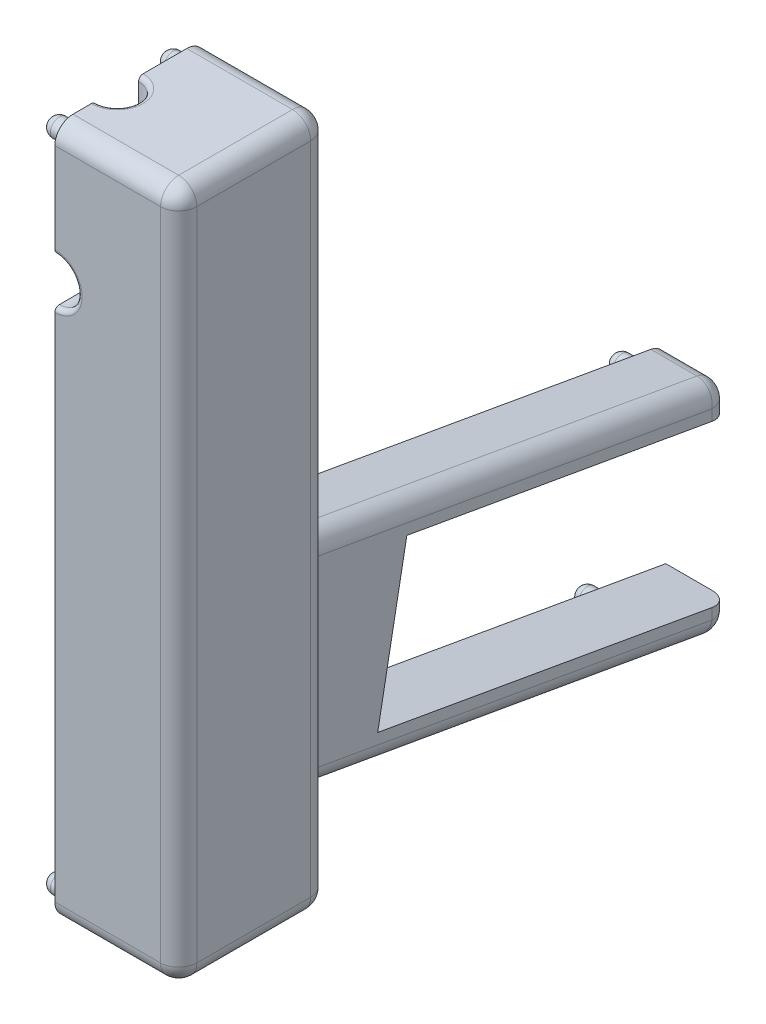
SolidWorks part; units mm, degrees
ref_plane "Front Plane" through (0, 0, 0) normal (0, 0, 1) x (1, 0, 0)
ref_plane "Top Plane" through (0, 0, 0) normal (0, 1, 0) x (1, 0, 0)
ref_plane "Right Plane" through (0, 0, 0) normal (1, 0, 0) x (0, 0, -1)
sketch "Sketch1" plane through (0, 0, 0) normal (0, 1, 0) x (1, 0, 0)
  line L1 (0, 0) -> (27.305, 0)
  line L2 (0, 0) -> (0, 33.1)
  line L3 (0, 33.1) -> (27.305, 33.1)
  line L4 (27.305, 0) -> (27.305, 33.1)
  dimension "D1" = 27.305
  dimension "D2" = 33.1
extrude "Boss-Extrude1" add sketch "Sketch1" along normal blind 152.4
sketch "Sketch2" plane through (0, 0, 0) normal (-1, 0, 0) x (0, 0, 1)
  line L0 (0, 152.4) -> (0, 0) construction
  line L1 (-6.35, 146.05) -> (-26.75, 146.05)
  line L2 (-6.35, 146.05) -> (-6.35, 6.35)
  line L3 (-6.35, 6.35) -> (-26.75, 6.35)
  line L4 (-26.75, 146.05) -> (-26.75, 6.35)
  line L5 (-33.1, 152.4) -> (0, 152.4) construction
  line L6 (-33.1, 152.4) -> (-33.1, 0) construction
  line L7 (-33.1, 0) -> (0, 0) construction
  dimension "D1" = 6.35
  dimension "D2" = 6.35
  dimension "D3" = 6.35
  dimension "D4" = 6.35
extrude "Cut-Extrude1" cut sketch "Sketch2" against normal blind 19.05
sketch "Sketch3" plane through (0, 0, 0) normal (0, 0, 1) x (1, 0, 0)
  line L0 (0, 152.4) -> (0, 0) construction
  line L1 (0, 127.555) -> (0, 117.555)
  arc A0 (0, 127.555) -> (0, 117.555) centre (0, 122.555) cw
  dimension "D1" = 29.845
extrude "HitLED" cut sketch "Sketch3" against normal up to next
sketch "Sketch6" plane through (19.05, 0, 0) normal (-1, 0, 0) x (0, 0, 1)
  line L0 (-15.7, 107.95) -> (-15.7, 33.02)
  line L1 (-9.35, 107.95) -> (-23.75, 107.95)
  line L2 (-9.35, 107.95) -> (-9.35, 33.02)
  line L3 (-9.35, 33.02) -> (-23.75, 33.02)
  line L4 (-23.75, 107.95) -> (-23.75, 33.02)
  line L5 (-17.4, 33.02) -> (-17.4, 107.95)
  line L7 (-6.35, 146.05) -> (-26.75, 146.05) construction
  line L8 (-26.75, 146.05) -> (-26.75, 6.35) construction
  line M8 (-6.35, 146.05) -> (-26.75, 146.05)
  dimension "D1" = 38.1
  dimension "D2" = 3
  dimension "D3" = 1.7
  dimension "D4" = 6.35
  dimension "D5" = 6.35
  dimension "D6" = 74.93
extrude "PCB" add sketch "Sketch6" along normal blind 6.35 contours L3 L2 L0 M8 | L3 L5 L1 L4 region at (19.05, 70.485, -12.525) region at (19.05, 70.485, -20.575)
sketch "Sketch16" plane through (0, 0, 0) normal (-1, 0, 0) x (0, 0, 1)
  line L1 (-33.1, 152.4) -> (0, 152.4) construction
  line L2 (0, 117.555) -> (0, 0) construction
  line L3 (-33.1, 0) -> (0, 0) construction
  line L5 (-33.1, 152.4) -> (-33.1, 0) construction
  circle A0 centre (-4, 148.4) radius 2
  circle A1 centre (-4, 4) radius 2
  circle A2 centre (-29.1, 148.4) radius 2
  circle A3 centre (-29.1, 4) radius 2
  dimension "D1" = 4
  dimension "D3" = 4
  dimension "D2" = 4
  dimension "D4" = 4
extrude "PressFit" add sketch "Sketch16" along normal blind 5
fillet "Fillet-PressFit" radius 2 4 edges at (-5, 4, -27.1) (-5, 4, -2) (-5, 148.4, -27.1) (-5, 148.4, -2)
sketch "Sketch23" plane through (0, 0, -25.4) normal (-1, 0, 0) x (0, 0, 1)
  line L4 (-7.7, 61.1358) -> (-7.7, 12.7)
  line L5 (-7.7, 12.7) -> (-109.3, -5.2148)
  line L6 (-109.3, -5.2148) -> (-109.3, 43.221)
  line L7 (-109.3, 43.221) -> (-7.7, 61.1358)
  dimension "D1" = 47.7
  dimension "D2" = 12.7
extrude "Butt" add sketch "Sketch23" against normal blind 14.175
sketch "Sketch20" plane through (0, 0, 0) normal (-1, 0, 0) x (0, 0, 1)
  line L0 (-63.4356, 49.3389) -> (-57.0033, 14.9332)
  line L1 (-63.4356, 49.3389) -> (-130.4061, 37.5302)
  line L2 (-57.0033, 14.9332) -> (-123.9738, 3.1245)
  line L6 (-130.4061, 37.5302) -> (-134.7, 36.7731)
  line L10 (-123.9738, 3.1245) -> (-134.7, 1.2331)
  line L11 (-134.7, 1.2331) -> (-134.7, 36.7731)
  dimension "D2" = 35
extrude "BatteryPack" cut sketch "Sketch20" against normal blind 14.175
sketch "Sketch22" plane through (0, 0, 0) normal (-1, 0, 0) x (0, 0, 1)
  line L0 (-63.4356, 49.3389) -> (-134.7, 36.7731) construction
  line L2 (-134.7, 1.2331) -> (-57.0033, 14.9332) construction
  line L4 (-57.0033, 14.9332) -> (-63.4356, 49.3389) construction
  circle A0 centre (-128.067, 41.1666) radius 2
  circle A1 centre (-120.4429, 0.5231) radius 2
  dimension "D1" = 3.175
  dimension "D2" = 3.175
  dimension "D3" = 65.0325
  dimension "D4" = 65.0073
extrude "PressFit - Bottom" add sketch "Sketch22" along normal blind 5
sketch "Sketch25" plane through (0, 146.05, 0) normal (0, -1, 0) x (1, 0, 0)
  line L0 (0, -6.35) -> (0, -26.75) construction
  line L1 (0, -9.05) -> (0, -18.45)
  line L2 (19.05, -26.75) -> (0, -26.75) construction
  arc A0 (0, -9.05) -> (0, -18.45) centre (0, -13.75) cw
  dimension "D1" = 13
extrude "IRLED" cut sketch "Sketch25" against normal up to next
fillet "Fillet - Body" radius 4 17 edges at (14.175, -1.9908, -134.7) (14.175, 39.997, -134.7) (7.0875, 43.221, -134.7) (7.0875, -5.2148, -134.7) (14.175, 52.1784, -83.9) (14.175, 3.7426, -83.9) (7.0875, 12.7, -33.1) (14.175, 36.9179, -33.1) (7.0875, 61.1358, -33.1) (13.6525, 152.4, -33.1) (13.6525, 152.4, 0) (27.305, 152.4, -16.55) (27.305, 76.2, -33.1) (27.305, 0, -16.55) (13.6525, 0, -33.1) (13.6525, 0, 0) (27.305, 76.2, 0)
fillet "Fillet-PressFit-Bottom" radius 2 2 edges at (-5, 0.5231, -118.4429) (-5, 41.1666, -126.067)
fillet "Fillet-LED's" radius 1 2 edges at (4.7, 152.4, -13.75) (5, 122.555, 0)
sketch "Sketch26" plane through (0, 0, 0) normal (-1, 0, 0) x (0, 0, 1)
  line L0 (-46.718, 58.7346) -> (-53.6116, 57.5191)
  line L1 (-53.6116, 57.5191) -> (-52.9865, 53.9738)
  line L2 (-52.9865, 53.9738) -> (-46.0928, 55.1893)
  line L3 (-46.0928, 55.1893) -> (-46.718, 58.7346)
  line L4 (-36.4054, 60.553) -> (-131.3946, 43.8039) construction
  point P6 (-46.4054, 56.962)
  dimension "D1" = 3.6
  dimension "D2" = 7
  dimension "D3" = 10
  dimension "D4" = 0
extrude "Cut-Extrude2" cut sketch "Sketch26" against normal blind 3.5
sketch "Sketch27" plane through (0, 0, 0) normal (-1, 0, 0) x (0, 0, 1)
  line L0 (-40.1594, 56.2356) -> (-58.92, 52.9276)
  line L1 (-58.92, 52.9276) -> (-58.6248, 51.2534)
  line L2 (-58.6248, 51.2534) -> (-39.8642, 54.5614)
  line L3 (-39.8642, 54.5614) -> (-40.1594, 56.2356)
  line L6 (-52.9865, 53.9738) -> (-46.0928, 55.1893) construction
  line L7 (-46.0928, 55.1893) -> (-46.718, 58.7346) construction
  dimension "D1" = 1.7
  dimension "D2" = 19.05
  dimension "D3" = 6.025
extrude "Cut-Extrude3" cut sketch "Sketch27" against normal blind 12.065
sketch "Sketch28" plane through (0, 0, 0) normal (-1, 0, 0) x (0, 0, 1)
  line L0 (-46.29, 53.4283) -> (-52.1989, 52.3864)
  line L1 (-46.29, 53.4283) -> (-41.9488, 28.8081)
  line L2 (-52.1989, 52.3864) -> (-47.8577, 27.7662)
  line L3 (-41.9488, 28.8081) -> (-47.8577, 27.7662)
  line L4 (-58.6248, 51.2534) -> (-39.8642, 54.5614) construction
  line L5 (-39.8642, 54.5614) -> (-40.1594, 56.2356) construction
  dimension "D1" = 6
  dimension "D2" = 6.525
  dimension "D3" = 25
extrude "Cut-Extrude4" cut sketch "Sketch28" against normal blind 7.825
